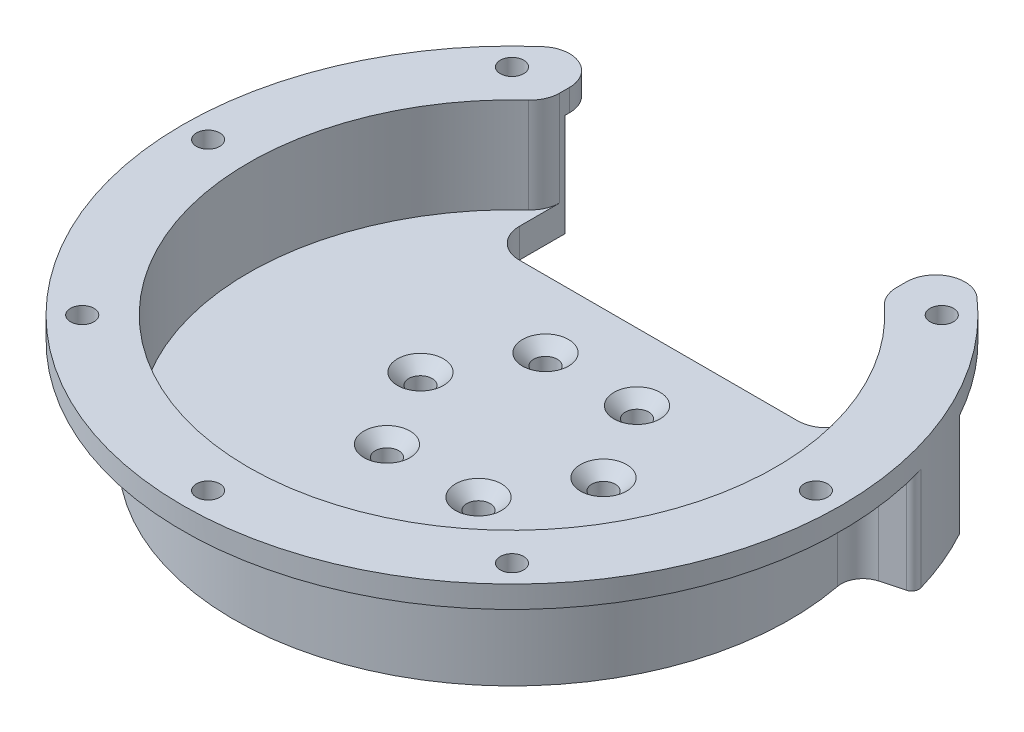
SolidWorks part; units mm, degrees
ref_plane "Спереди" through (0, 0, 0) normal (0, 0, 1) x (1, 0, 0)
ref_plane "Сверху" through (0, 0, 0) normal (0, 1, 0) x (1, 0, 0)
ref_plane "Справа" through (0, 0, 0) normal (1, 0, 0) x (0, 0, -1)
ref_plane "Плоскость4" through (0, 17, 0) normal (0, 1, 0) x (1, 0, 0)
sketch "Эскиз1" plane through (0, 17, 0) normal (0, 1, 0) x (1, 0, 0)
  line L0 (23, 30.8545) -> (23, 27.6948)
  line L1 (-23, 27.6948) -> (-23, 30.8545)
  arc A0 (23, 27.6948) -> (-23, 27.6948) centre (0, 0) ccw
  arc A1 (-23, 30.8545) -> (-29.6341, 33.8647) centre (-27, 30.8545) ccw
  arc A2 (-29.6341, 33.8647) -> (29.6341, 33.8647) centre (0, 0) ccw
  arc A3 (29.6341, 33.8647) -> (23, 30.8545) centre (27, 30.8545) ccw
extrude "Бобышка-Вытянуть1" add sketch "Эскиз1" against normal blind 3
sketch "Эскиз2" plane through (0, 14, 0) normal (0, -1, 0) x (1, 0, 0)
  line L0 (-23, -27.6948) -> (-23, -30.249)
  line L1 (36.7052, -9.8351) -> (43.4667, -11.6469)
  line L2 (38.9711, -22.5) -> (32.909, -19)
  line L3 (23, -30.249) -> (23, -27.6948)
  arc A0 (-23, -30.249) -> (36.7052, -9.8351) centre (0, 0) cw
  arc A1 (43.4667, -11.6469) -> (38.9711, -22.5) centre (0, 0) cw
  arc A2 (32.909, -19) -> (23, -30.249) centre (0, 0) cw
  arc A3 (23, -27.6948) -> (-23, -27.6948) centre (0, 0) cw
extrude "Бобышка-Вытянуть2" add sketch "Эскиз2" along normal blind 14
ref_plane "Плоскость5" through (0, 0, 0) normal (0, -1, 0) x (1, 0, 0)
ref_plane "Плоскость6" through (0, 4, 0) normal (0, 1, 0) x (1, 0, 0)
sketch "Эскиз4" plane through (0, 4, 0) normal (0, 1, 0) x (1, 0, 0)
  line L0 (-23, 27.6948) -> (-23, 20)
  line L1 (-23, 20) -> (23, 20)
  line L2 (23, 20) -> (23, 27.6948)
  arc A0 (23, 27.6948) -> (-23, 27.6948) centre (0, 0) ccw
extrude "Вырез-Вытянуть1" cut sketch "Эскиз4" against normal up to surface up to plane "Плоскость5"
ref_plane "Плоскость7" through (0, 0, 0) normal (0, 0, -1) x (-1, 0, 0)
sketch "Эскиз5" plane through (0, 0, 0) normal (0, 0, -1) x (-1, 0, 0)
  line L0 (-36, 4) -> (0, 4)
  line L1 (0, 4) -> (0, 17)
  line L2 (0, 17) -> (-36, 17)
  line L3 (-36, 17) -> (-36, 4)
  line L4 (0, 4) -> (0, 17) construction
revolve "Вырез-Повернуть1" cut sketch "Эскиз5" angle 360 about L4 reverse direction yes
hole_wizard "Диаметр отверстия Ø3.0 (3)1" positions "Эскиз7" profile "Эскиз6" hole size "Ø3.0" standard "Ansi Metric"
sketch "Эскиз7" plane through (0, 0, 0) normal (0, -1, 0) x (-1, 0, 0)
  point P0 (0, -12.5)
  point P1 (0, 12.5)
sketch "Эскиз6" plane through (0, 0, 12.5) normal (1, 0, 0) x (0, 0, -1)
  line L0 (0, 0) -> (0, 3.9013)
  line L1 (0, 3.9013) -> (1.5, 3)
  line L2 (1.5, 3) -> (1.5, 0)
  line L5 (1.5, 0) -> (0, 0)
  line L10 (0, 3.9013) -> (-1.5, 3) construction
  line L11 (0, -6.35) -> (0, 107.95) construction
  dimension "Диаметр отверстия" = 3
  dimension "Глубина отверстия" = 3
  dimension "Угол заточки сверла" = 118
hole_wizard "Диаметр отверстия Ø3.2 (3.2)1" positions "Эскиз9" profile "Эскиз8" hole size "Ø3.2" standard "Ansi Metric"
sketch "Эскиз9" plane through (0, 17, 0) normal (0, 1, 0) x (1, 0, 0)
  point P0 (29.3449, -29.3449)
  point P1 (0, -41.5)
  point P2 (-29.3449, -29.3449)
  point P3 (-41.5, 0)
  point P4 (-29.3449, 29.3449)
  point P5 (29.3449, 29.3449)
  point P6 (41.5, 0)
sketch "Эскиз8" plane through (29.3449, 17, 29.3449) normal (1, 0, 0) x (0, 0, 1)
  line L0 (0, 0) -> (0, 17)
  line L1 (0, 17) -> (1.6, 17)
  line L2 (1.6, 17) -> (1.6, 0)
  line L5 (1.6, 0) -> (0, 0)
  line L11 (0, -6.35) -> (0, 107.95) construction
  dimension "Диаметр сквозного отверстия" = 3.2
  dimension "Глубина сквозного отверстия" = 17
hole_wizard "Диаметр отверстия Ø3.2 (3.2)2" positions "Эскиз11" profile "Эскиз10" hole size "Ø3.2" standard "Ansi Metric"
sketch "Эскиз11" plane through (0, 4, 0) normal (0, 1, 0) x (1, 0, 0)
  point P0 (-6.25, -10.8253)
  point P1 (6.25, -10.8253)
  point P2 (12.5, 0)
  point P3 (6.25, 10.8253)
  point P4 (-6.25, 10.8253)
  point P5 (-12.5, 0)
sketch "Эскиз10" plane through (-6.25, 4, 10.8253) normal (1, 0, 0) x (0, 0, 1)
  line L0 (0, 0) -> (0, 4)
  line L1 (0, 4) -> (1.6, 4)
  line L2 (1.6, 4) -> (1.6, 0)
  line L5 (1.6, 0) -> (0, 0)
  line L11 (0, -6.35) -> (0, 107.95) construction
  dimension "Диаметр сквозного отверстия" = 3.2
  dimension "Глубина сквозного отверстия" = 4
chamfer "Фаска1" distance 1.55 angle 45 6 edges at (-12.5, 4, 1.6) (6.25, 4, 12.4253) (-6.25, 4, 12.4253) (6.25, 4, -9.2253) (12.5, 4, 1.6) (-6.25, 4, -9.2253)
fillet "Скругление1" radius 1 2 edges at (38.9711, 7, -22.5) (43.4667, 7, -11.6469) tangent propagation no
fillet "Скругление2" radius 3 2 edges at (36.7052, 7, -9.8351) (32.909, 7, -19) tangent propagation no
fillet "Скругление3" radius 4 4 edges at (23, 10.5, -27.6948) (-23, 10.5, -27.6948) (23, 2, -20) (-23, 2, -20) tangent propagation no
